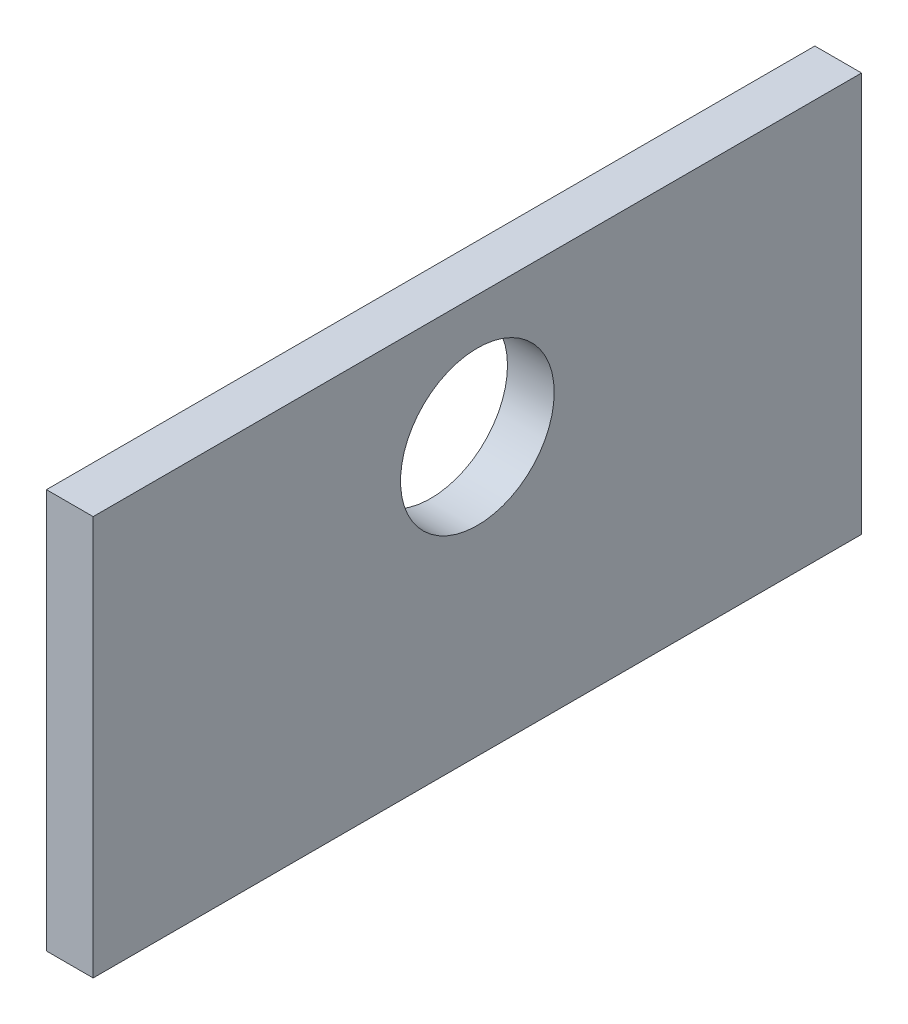
SolidWorks part; units mm, degrees
material "6061 Alloy"
ref_plane "Front Plane" through (0, 0, 0) normal (0, 0, 1) x (1, 0, 0)
ref_plane "Top Plane" through (0, 0, 0) normal (0, 1, 0) x (1, 0, 0)
ref_plane "Right Plane" through (0, 0, 0) normal (1, 0, 0) x (0, 0, -1)
sketch "Sketch1" plane through (0, 0, 0) normal (1, 0, 0) x (0, 0, -1)
  line L0 (0, -28.575) -> (0, 12.7) construction
  line L1 (-39.6875, 12.7) -> (39.6875, 12.7)
  line L2 (-39.6875, 12.7) -> (-39.6875, -28.575)
  line L3 (-39.6875, -28.575) -> (39.6875, -28.575)
  line L4 (39.6875, 12.7) -> (39.6875, -28.575)
  circle A0 centre (0, 0) radius 7.9375
  dimension "D3" = 15.875
  dimension "D1" = 39.6875
  dimension "D2" = 12.7
  dimension "D4" = 28.575
  dimension "D5" = 39.6875
extrude "Boss-Extrude1" add sketch "Sketch1" along normal blind 4.826
